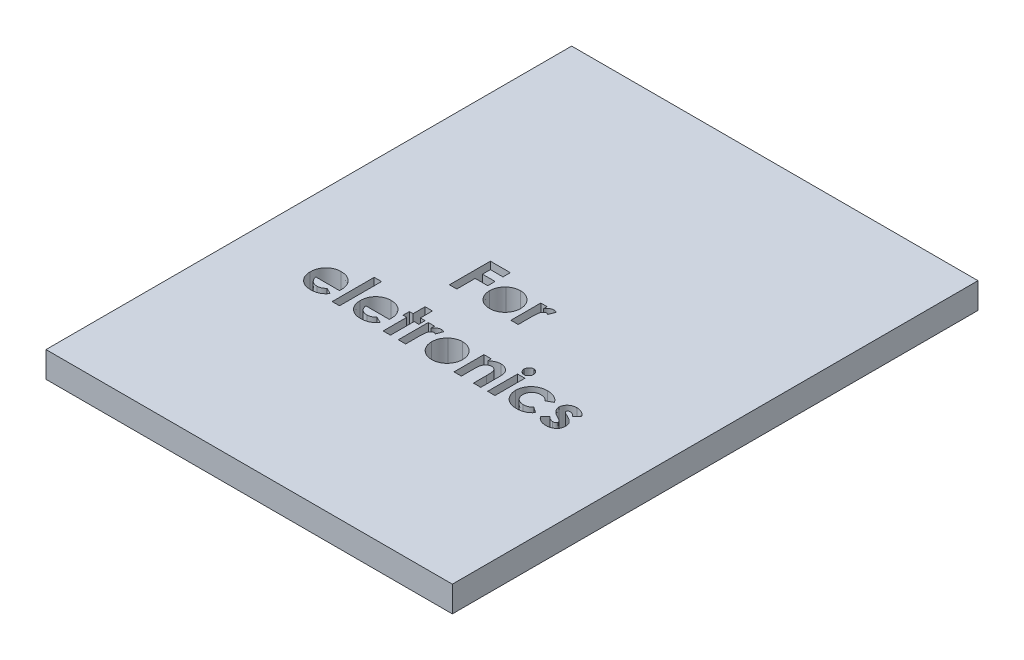
SolidWorks part; units mm, degrees
ref_plane "Front" through (0, 0, 0) normal (0, 0, 1) x (1, 0, 0)
ref_plane "Top" through (0, 0, 0) normal (0, 1, 0) x (1, 0, 0)
ref_plane "Right" through (0, 0, 0) normal (1, 0, 0) x (0, 0, -1)
sketch "Sketch1" plane through (0, 0, 0) normal (0, 1, 0) x (1, 0, 0)
  line L1 (-63, 81.5) -> (0, 81.5)
  line L2 (-63, 81.5) -> (-63, 0)
  line L3 (-63, 0) -> (0, 0)
  line L4 (0, 81.5) -> (0, 0)
  dimension "D1" = 81.5
  dimension "D2" = 63
extrude "Boss-Extrude1" add sketch "Sketch1" along normal blind 4
sketch "Sketch2" plane through (0, 4, 0) normal (0, 1, 0) x (1, 0, 0)
  text T0 "<b>     For</b>\r\n<b>eletronics</b>"
extrude "Cut-Extrude1" cut sketch "Sketch2" against normal through all
